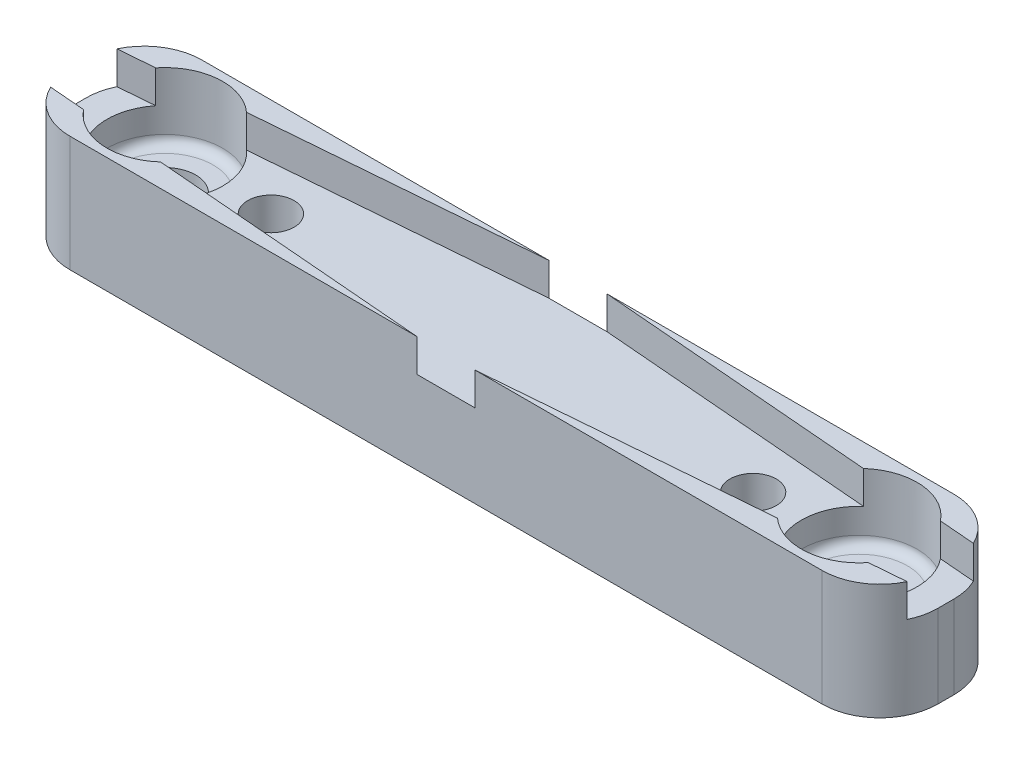
SolidWorks part; units mm, degrees
ref_plane "前视基准面" through (0, 0, 0) normal (0, 0, 1) x (1, 0, 0)
ref_plane "上视基准面" through (0, 0, 0) normal (0, 1, 0) x (1, 0, 0)
ref_plane "右视基准面" through (0, 0, 0) normal (1, 0, 0) x (0, 0, -1)
sketch "草图2" plane through (0, 0, 4.5) normal (0, 1, 0) x (1, 0, 0)
  line L11 (22.5, -3.4214) -> (22.5, 3.4214)
  line L12 (-3.9065, -3.4214) -> (3.9065, -3.4214)
  line L13 (22.5, 3.4214) -> (3.9065, 3.4214)
  line L14 (-22.5, -3.4214) -> (-22.5, 3.4214)
  line L15 (-3.9065, 3.4214) -> (3.9065, 3.4214)
  line L16 (22.5, -3.4214) -> (-22.5, 3.4214) construction
  line L17 (22.5, -3.4214) -> (3.9065, -3.4214)
  line L18 (-3.9065, -3.4214) -> (-22.5, -3.4214)
  line L19 (0, 0) -> (0, 12.7469) construction
  line L20 (-3.9065, 3.4214) -> (-22.5, 3.4214)
  line L21 (22.5, 3.4214) -> (-22.5, -3.4214) construction
  circle A2 centre (-12.5, 0) radius 1.2
  circle A3 centre (12.5, 0) radius 1.2
  circle A4 centre (-18, 0) radius 1.6
  circle A5 centre (18, 0) radius 1.6
  point P17 (0, 0)
extrude "凸台-拉伸2" add sketch "草图2" along normal blind 6
sketch "草图3" plane through (0, 0, 0) normal (0, -1, 0) x (-1, 0, 0)
  line L1 (0, 0) -> (0, 10.9531) construction
  circle A2 centre (-12.5, -4.5) radius 3
  circle A3 centre (12.5, -4.5) radius 3
extrude "切除-拉伸1" cut sketch "草图3" against normal blind 1
fillet "圆角2" radius 3 4 edges at (22.5, 3, 1.0786) (22.5, 3, 7.9214) (-22.5, 3, 7.9214) (-22.5, 3, 1.0786)
sketch "草图4" plane through (0, 6, 0) normal (0, 1, 0) x (1, 0, 0)
  line L8 (43.0791, -4.5) -> (0, -8.0462)
  line L9 (-43.0791, -4.5) -> (0, -0.9538)
  line L10 (17.5, -4.5) -> (7.0116, -4.5) construction
  line L11 (0, -0.9538) -> (43.0791, -4.5)
  line L12 (0, -4.5) -> (43.0791, -4.5) construction
  line L13 (0, -8.0462) -> (-43.0791, -4.5)
  line L14 (0, -4.5) -> (0, -9.0689) construction
extrude "切除-拉伸2" cut sketch "草图4" against normal blind 1.7
sketch "草图5" plane through (0, 4.3, 0) normal (0, 1, 0) x (1, 0, 0)
  circle A0 centre (-18, -4.5) radius 3
  circle A1 centre (18, -4.5) radius 3
extrude "切除-拉伸3" cut sketch "草图5" against normal blind 1.8 and the other way through all
fillet "圆角3" radius 0.5 4 edges at (18, 2.5, 7.5) (-18, 2.5, 7.5) (-12.5, 1, 7.5) (12.5, 1, 1.5)
ref_plane "基准面1" through (0, 0, 4.5) normal (0, 0, 1) x (1, 0, 0)
ref_axis "基准轴1" through (0, 6.3, 4.5) along (0, -1, 0)
